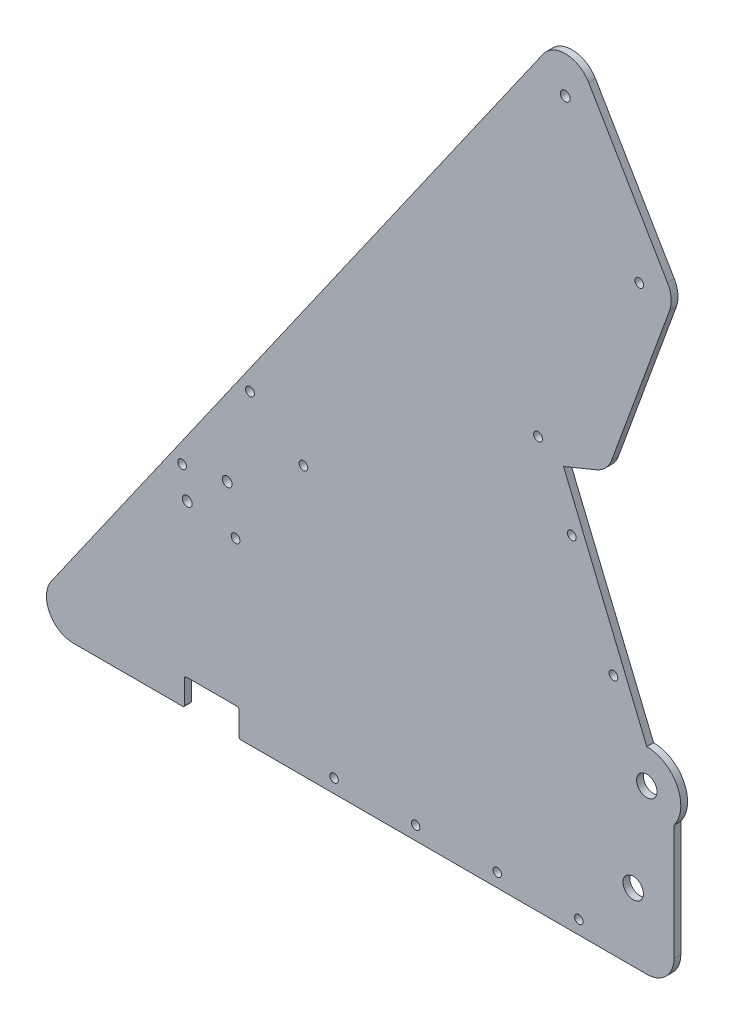
SolidWorks part; units mm, degrees
other "Markup1"
sketch "Sketch5"
ref_plane "Front Plane" through (0, 0, 0) normal (0, 0, 1) x (1, 0, 0)
ref_plane "Top Plane" through (0, 0, 0) normal (0, 1, 0) x (1, 0, 0)
ref_plane "Right Plane" through (0, 0, 0) normal (1, 0, 0) x (0, 0, -1)
sketch "Sketch1" plane through (0, 0, 0) normal (0, 0, 1) x (1, 0, 0)
  line L0 (0, 0) -> (76.2, 0)
  line L1 (304.8, 0) -> (304.8, 66.675)
  line L2 (254.9547, 364.1131) -> (0, 0)
  line L3 (304.8, 279.4) -> (254.9547, 364.1131)
  line L4 (76.2, 0) -> (76.2, 12.7)
  line L5 (76.2, 12.7) -> (101.6, 12.7)
  line L6 (101.6, 12.7) -> (101.6, 0)
  line L7 (101.6, 0) -> (304.8, 0)
  line L9 (292.1, 92.075) -> (253.2194, 185.9412)
  line L10 (253.2194, 185.9412) -> (273.7526, 194.4463)
  line L11 (273.7526, 194.4463) -> (304.8, 279.4)
  arc A0 (304.8, 66.675) -> (292.1, 92.075) centre (292.1, 76.2) ccw
  point P11 (262.2053, 188.154)
  point P15 (292.1, 95.25)
  point P16 (0, 0)
  point P17 (0, 0)
  point P18 (274.3524, 197.8697)
  point P19 (0, 0)
  dimension "D7" = 12.7
  dimension "D8" = 76.2
  dimension "D10" = 31.75
  dimension "D1" = 304.8
  dimension "D2" = 279.4
  dimension "D3" = 55
  dimension "D4" = 444.5
  dimension "D5" = 76.2
  dimension "D6" = 25.4
  dimension "D9" = 292.1
  dimension "D11" = 101.6
  dimension "D12" = 22.5
  dimension "D13" = 22.225
extrude "Boss-Extrude1" add sketch "Sketch1" along normal blind 3.175
sketch "Sketch2" plane through (0, 0, 3.175) normal (0, 0, 1) x (1, 0, 0)
  line L0 (254.9547, 364.1131) -> (0, 0) construction
  line L1 (101.6, 0) -> (304.8, 0) construction
  line L2 (292.1, 92.075) -> (253.2194, 185.9412) construction
  line L3 (253.2194, 185.9412) -> (273.7526, 194.4463) construction
  line L4 (292.1, 92.075) -> (253.2194, 185.9412) construction
  line L5 (304.8, 279.4) -> (288.6002, 277.9261) construction
  line L6 (285.4785, 312.2373) -> (291.7219, 243.6149) construction
  line L7 (304.8, 279.4) -> (254.9547, 364.1131) construction
  line L8 (273.7526, 194.4463) -> (304.8, 279.4) construction
  line L9 (273.7526, 194.4463) -> (304.8, 279.4) construction
  circle A0 centre (77.4583, 84.0518) radius 2.286
  circle A1 centre (254, 336.1795) radius 2.286
  circle A2 centre (96.1158, 101.2872) radius 2.286
  circle A3 centre (257.0729, 160.0446) radius 2.032
  circle A4 centre (292.1, 76.2) radius 4.7625
  circle A5 centre (184.15, 6.35) radius 1.9682
  circle A6 centre (222.25, 6.35) radius 1.9682
  circle A7 centre (260.35, 6.35) radius 1.9682
  circle A8 centre (276.5132, 113.1115) radius 2.032
  circle A18 centre (288.6002, 277.9261) radius 2.032
  circle A26 centre (285.75, 31.75) radius 4.7625
  circle A28 centre (106.7599, 143.0587) radius 2.032
  circle A29 centre (106.7599, 143.0587) radius 2.032
  arc A30 (304.8, 66.675) -> (292.1, 92.075) centre (292.1, 76.2) ccw construction
  circle A31 centre (241.3, 192.0875) radius 2.032
  circle A34 centre (75.0727, 97.8047) radius 2.032
  circle A35 centre (75.0727, 97.8047) radius 2.032
  circle A37 centre (100.0405, 80.3221) radius 2.032
  circle A38 centre (100.0405, 80.3221) radius 2.032
  circle A39 centre (131.7277, 125.5761) radius 2.032
  circle A40 centre (131.7277, 125.5761) radius 2.032
  circle A41 centre (146.05, 6.35) radius 1.9682
  point P59 (0, 0)
  point P60 (288.6002, 277.9261)
  point P61 (296.5502, 257.67)
  point P64 (295.7871, 255.6601)
  dimension "D3" = 4.572
  dimension "D5" = 4.572
  dimension "D9" = 4.572
  dimension "D14" = 3.9364
  dimension "D20" = 9.525
  dimension "D23" = 9.525
  dimension "D18" = 4.064
  dimension "D26" = 4.064
  dimension "D2" = 15.24
  dimension "D4" = 254
  dimension "D6" = 15.24
  dimension "D7" = 25.4
  dimension "D8" = 20.6375
  dimension "D15" = 146.05
  dimension "D16" = 6.35
  dimension "D21" = 44.45
  dimension "D22" = 6.35
  dimension "D19" = 160.3375
  dimension "D24" = 44.45
  dimension "D25" = 6.35
  dimension "D27" = 25.4
  dimension "D28" = 50.8
  dimension "D29" = 6.35
  dimension "D30" = 38.1
  dimension "D31" = 38.1
  dimension "D32" = 114.3
  dimension "D10" = 0.127
  dimension "D12" = 0.127
  dimension "D13" = 0.127
  dimension "D11" = 0.127
  dimension "D17" = 4
extrude "Cut-Extrude1" cut sketch "Sketch2" against normal through all
fillet "Fillet1" radius 12.7 5 edges at (0, 0, 1.5875) (304.8, 0, 1.5875) (254.9547, 364.1131, 1.5875) (273.7526, 194.4463, 1.5875) (304.8, 279.4, 1.5875)
fillet "Fillet2" radius 0.7937 4 edges at (101.6, 0, 1.5875) (101.6, 12.7, 1.5875) (76.2, 0, 1.5875) (76.2, 12.7, 1.5875)
equation "\"D6@Sketch2\"=\"D2@Sketch2\""
